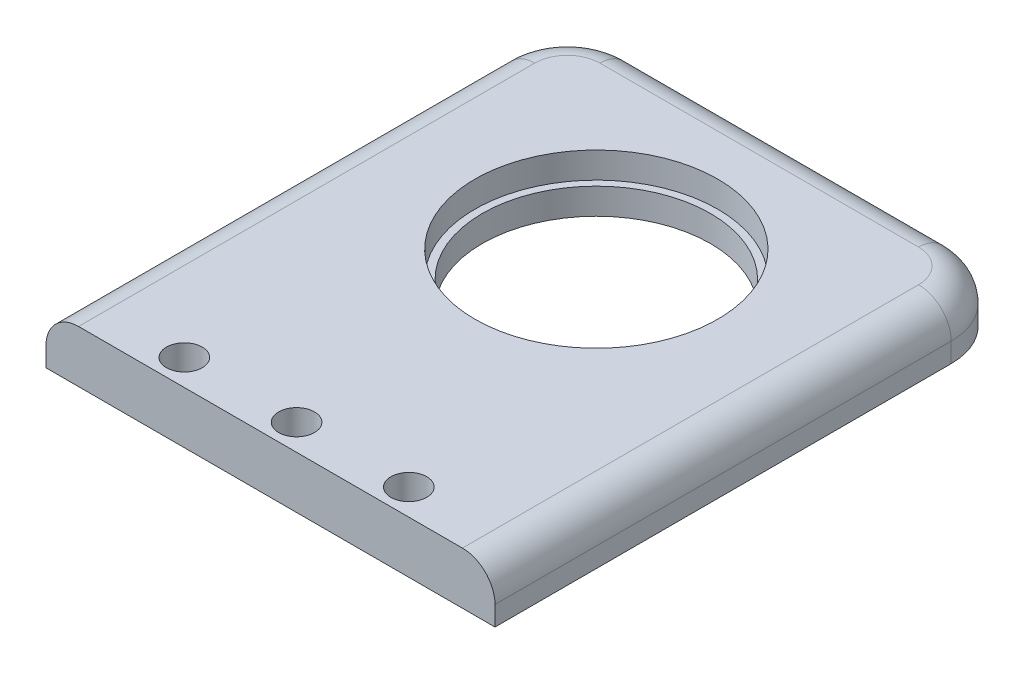
SolidWorks part; units mm, degrees
ref_plane "Front Plane" through (0, 0, 0) normal (0, 0, 1) x (1, 0, 0)
ref_plane "Top Plane" through (0, 0, 0) normal (0, 1, 0) x (1, 0, 0)
ref_plane "Right Plane" through (0, 0, 0) normal (1, 0, 0) x (0, 0, -1)
sketch "Sketch1" plane through (0, 0, 0) normal (0, 1, 0) x (1, 0, 0)
  line L0 (-33.7277, -40) -> (35.1723, -40)
  line L1 (-33.7277, -40) -> (-33.7277, 40)
  line L2 (-33.7277, 40) -> (35.1723, 40)
  line L3 (35.1723, -40) -> (35.1723, 40)
  circle A0 centre (0.7223, 10) radius 18.63
  circle A1 centre (0.7223, -36) radius 2.75
  circle A2 centre (-16.5027, -36) radius 2.75
  circle A3 centre (17.9473, -36) radius 2.75
  dimension "D1" = 30
  dimension "D2" = 68.9
  dimension "D3" = 34.45
  dimension "D4" = 34.45
  dimension "D5" = 17.225
  dimension "D6" = 17.225
  dimension "D7" = 4
extrude "Boss-Extrude1" add sketch "Sketch1" along normal blind 8
fillet "Fillet1" radius 10 2 edges at (35.1723, 4, -40) (-33.7277, 4, -40)
fillet "Fillet2" radius 5 5 edges at (32.2434, 8, -37.0711) (0.7223, 8, -40) (-30.7987, 8, -37.0711) (35.1723, 8, 5) (-33.7277, 8, 5)
sketch "Sketch2" plane through (0, 0, 0) normal (0, -1, 0) x (1, 0, 0)
  circle A0 centre (0.7223, -10) radius 17.5
  circle A1 centre (0.7223, -10) radius 18.63
extrude "Boss-Extrude2" add sketch "Sketch2" against normal blind 4
